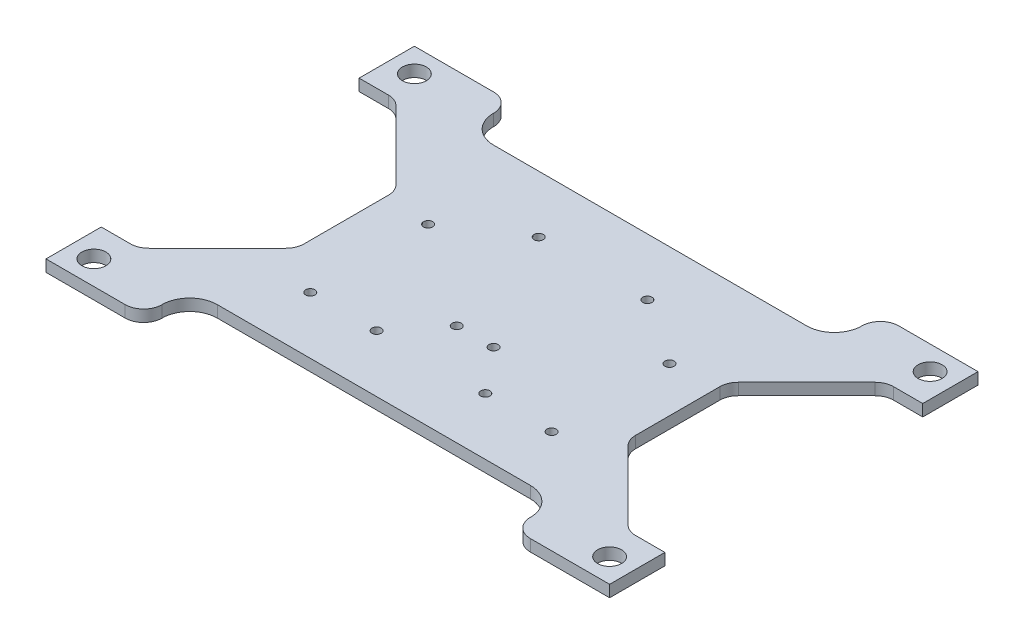
SolidWorks part; units mm, degrees
ref_plane "Front Plane" through (0, 0, 0) normal (0, 0, 1) x (1, 0, 0)
ref_plane "Top Plane" through (0, 0, 0) normal (0, 1, 0) x (1, 0, 0)
ref_plane "Right Plane" through (0, 0, 0) normal (1, 0, 0) x (0, 0, -1)
sketch "Sketch1" plane through (0, 0, 0) normal (0, 1, 0) x (1, 0, 0)
  line L0 (-76.5, 50) -> (76.5, -50) construction
  line L1 (-76.5, 50) -> (76.5, 50)
  line L2 (-76.5, 50) -> (-76.5, -50)
  line L3 (-76.5, -50) -> (76.5, -50)
  line L4 (76.5, 50) -> (76.5, -50)
  line L5 (-70, 43.5) -> (70, 43.5) construction
  line L6 (-70, 43.5) -> (-70, -43.5) construction
  line L7 (-70, -43.5) -> (70, -43.5) construction
  line L8 (70, 43.5) -> (70, -43.5) construction
  line L9 (70, 43.5) -> (-70, -43.5) construction
  circle A0 centre (-70, 43.5) radius 3.25
  circle A1 centre (70, 43.5) radius 3.25
  circle A2 centre (70, -43.5) radius 3.25
  circle A3 centre (-70, -43.5) radius 3.25
  dimension "D1" = 6.5
  dimension "D2" = 100
  dimension "D3" = 153
  dimension "D4" = 140
  dimension "D5" = 87
extrude "Boss-Extrude1" add sketch "Sketch1" along normal blind 3.175
sketch "Sketch2" plane through (0, 3.175, 0) normal (0, 1, 0) x (1, 0, 0)
  line L0 (0, 50) -> (0, -50) construction
  line L1 (76.5, 50) -> (-76.5, 50) construction
  line L2 (-76.5, -50) -> (76.5, -50) construction
  line L3 (-76.5, 0) -> (76.5, 0) construction
  line L4 (-76.5, 50) -> (-76.5, -50) construction
  line L5 (76.5, -50) -> (76.5, 50) construction
  line L6 (-76.5, 35) -> (-66.5, 35)
  line L7 (-66.5, 35) -> (-45, 13.5)
  line L8 (-45, 13.5) -> (-45, -13.5)
  line L9 (-76.5, 35) -> (-76.5, -35)
  line L10 (-66.5, -35) -> (-45, -13.5)
  line L11 (-76.5, -35) -> (-66.5, -35)
  line L12 (76.5, -35) -> (66.5, -35)
  line L13 (66.5, -35) -> (45, -13.5)
  line L14 (76.5, 35) -> (76.5, -35)
  line L15 (45, 13.5) -> (45, -13.5)
  line L16 (66.5, 35) -> (45, 13.5)
  line L17 (76.5, 35) -> (66.5, 35)
  point P18 (-45, 0)
  point P19 (45, 0)
  dimension "D1" = 70
  dimension "D2" = 10
  dimension "D3" = 90
  dimension "D4" = 45
extrude "Cut-Extrude1" cut sketch "Sketch2" against normal through all
sketch "Sketch3" plane through (0, 3.175, 0) normal (0, 1, 0) x (1, 0, 0)
  line L0 (0, 50) -> (0, -50) construction
  line L1 (76.5, 50) -> (-76.5, 50) construction
  line L2 (-76.5, -50) -> (76.5, -50) construction
  line L3 (45, 0) -> (-45, 0) construction
  line L4 (45, 13.5) -> (45, -13.5) construction
  line L5 (-45, -13.5) -> (-45, 13.5) construction
  line L6 (-42.5, 45) -> (-42.5, 60) construction
  line L7 (-50, 45) -> (-50, 60)
  line L8 (-35, 45) -> (-35, 60)
  line L9 (42.5, 45) -> (42.5, 60) construction
  line L10 (50, 45) -> (50, 60)
  line L11 (35, 45) -> (35, 60)
  line L12 (-42.5, -45) -> (-42.5, -60) construction
  line L13 (-50, -45) -> (-50, -60)
  line L14 (-35, -45) -> (-35, -60)
  line L15 (42.5, -45) -> (42.5, -60) construction
  line L16 (50, -45) -> (50, -60)
  line L17 (35, -45) -> (35, -60)
  arc A0 (-50, 45) -> (-35, 45) centre (-42.5, 45) ccw
  arc A1 (-35, 60) -> (-50, 60) centre (-42.5, 60) ccw
  arc A2 (50, 45) -> (35, 45) centre (42.5, 45) cw
  arc A3 (35, 60) -> (50, 60) centre (42.5, 60) cw
  arc A4 (-50, -45) -> (-35, -45) centre (-42.5, -45) cw
  arc A5 (-35, -60) -> (-50, -60) centre (-42.5, -60) cw
  arc A6 (50, -45) -> (35, -45) centre (42.5, -45) ccw
  arc A7 (35, -60) -> (50, -60) centre (42.5, -60) ccw
  point P14 (-42.5, 52.5)
  point P21 (42.5, 52.5)
  point P28 (-42.5, -52.5)
  point P35 (42.5, -52.5)
  dimension "D3" = 5
  dimension "D2" = 7.5
  dimension "D1" = 85
  dimension "D4" = 15
extrude "Cut-Extrude2" cut sketch "Sketch3" against normal through all
fillet "Fillet1" radius 5 16 edges at (-45, 1.5875, -13.5) (-45, 1.5875, 13.5) (-66.5, 1.5875, 35) (-50, 1.5875, 50) (-35, 1.5875, 50) (35, 1.5875, 50) (50, 1.5875, 50) (66.5, 1.5875, 35) (45, 1.5875, 13.5) (45, 1.5875, -13.5) (66.5, 1.5875, -35) (50, 1.5875, -50) (35, 1.5875, -50) (-35, 1.5875, -50) (-50, 1.5875, -50) (-66.5, 1.5875, -35)
sketch "Sketch4" plane through (0, 3.175, 0) normal (0, 1, 0) x (1, 0, 0)
  line L0 (-14.76, 0) -> (0, 0) construction
  line L1 (-32.76, 22) -> (-14.76, 22) construction
  line L2 (-32.76, 22) -> (-32.76, -22) construction
  line L3 (-32.76, -22) -> (-14.76, -22) construction
  line L4 (-14.76, 22) -> (-14.76, -22) construction
  line L5 (0, 50) -> (0, -50) construction
  line L6 (30, 50) -> (-30, 50) construction
  line L7 (-30, -50) -> (30, -50) construction
  line L8 (14.76, 22) -> (14.76, -22) construction
  line L9 (32.76, -22) -> (14.76, -22) construction
  line L10 (32.76, 22) -> (32.76, -22) construction
  line L11 (32.76, 22) -> (14.76, 22) construction
  circle A0 centre (-32.76, 10) radius 1.25
  circle A1 centre (-14.76, 22) radius 1.25
  circle A2 centre (-14.76, -22) radius 1.25
  circle A3 centre (-32.76, -22) radius 1.25
  circle A4 centre (32.76, -22) radius 1.25
  circle A5 centre (14.76, -22) radius 1.25
  circle A6 centre (14.76, 22) radius 1.25
  circle A7 centre (32.76, 10) radius 1.25
  dimension "D3" = 2.5
  dimension "D4" = 12
  dimension "D5" = 65.52
  dimension "D1" = 18
  dimension "D2" = 44
extrude "Cut-Extrude3" cut sketch "Sketch4" against normal through all
sketch "Sketch5" plane through (0, 3.175, 0) normal (0, 1, 0) x (1, 0, 0)
  line L0 (0, 50) -> (0, -10) construction
  line L1 (30, 50) -> (-30, 50) construction
  line L2 (5, -10) -> (-5, -10) construction
  circle A0 centre (-5, -10) radius 1.25
  circle A1 centre (5, -10) radius 1.25
  dimension "D3" = 2.5
  dimension "D1" = 10
  dimension "D2" = 60
extrude "Cut-Extrude4" cut sketch "Sketch5" against normal through all
sketch "Sketch6" plane through (0, 3.175, 0) normal (0, 1, 0) x (1, 0, 0)
  line L0 (30, 50) -> (-30, 50) construction
  line L1 (-42.5, 37.5) -> (42.5, 37.5)
  line L2 (-42.5, 37.5) -> (-42.5, 50)
  line L3 (-42.5, 50) -> (42.5, 50)
  line L4 (42.5, 37.5) -> (42.5, 50)
  line L5 (-30, -50) -> (30, -50) construction
  line L6 (-42.5, -37.5) -> (42.5, -37.5)
  line L7 (-42.5, -37.5) -> (-42.5, -50)
  line L8 (-42.5, -50) -> (42.5, -50)
  line L9 (42.5, -37.5) -> (42.5, -50)
  arc A0 (-50, 45) -> (-35, 45) centre (-42.5, 45) ccw construction
  arc A1 (35, 45) -> (50, 45) centre (42.5, 45) ccw construction
  arc A2 (-35, -45) -> (-50, -45) centre (-42.5, -45) ccw construction
  arc A3 (50, -45) -> (35, -45) centre (42.5, -45) ccw construction
extrude "Cut-Extrude5" cut sketch "Sketch6" against normal through all
